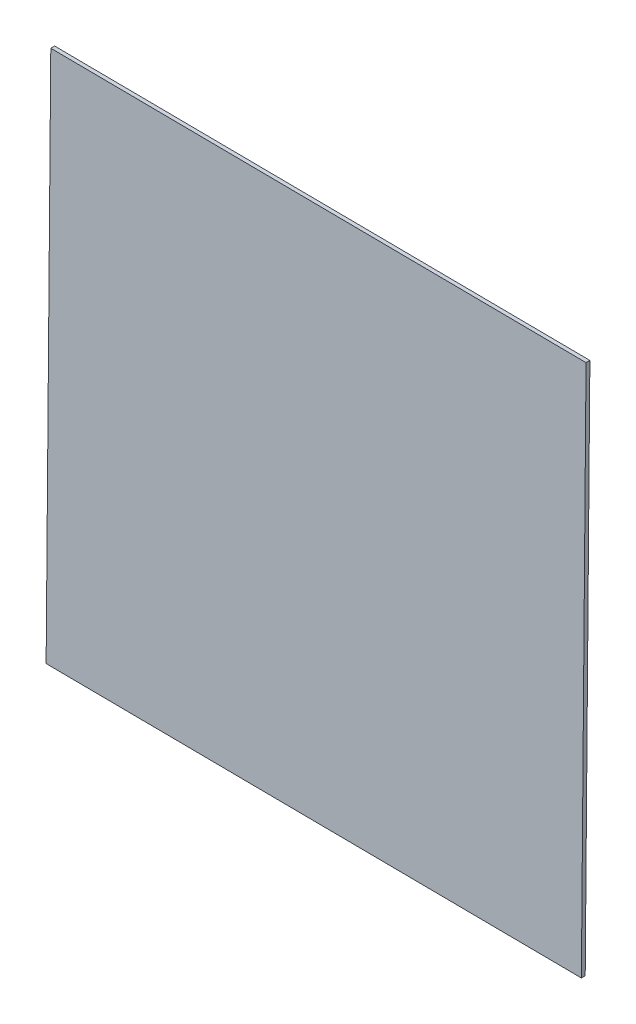
SolidWorks part; units mm, degrees
ref_plane "Front Plane" through (0, 0, 0) normal (0, 0, 1) x (1, 0, 0)
ref_plane "Top Plane" through (0, 0, 0) normal (0, 1, 0) x (1, 0, 0)
ref_plane "Right Plane" through (0, 0, 0) normal (1, 0, 0) x (0, 0, -1)
sketch "Sketch1" plane through (0, 0, 0) normal (0, 0, 1) x (1, 0, 0)
  line L4 (-97.7146, 56.2371) -> (-79.9861, 56.0824)
  line L5 (-79.9861, 56.0824) -> (-79.8314, 73.8109)
  line L6 (-79.8314, 73.8109) -> (-97.5599, 73.9656)
  line L7 (-97.5599, 73.9656) -> (-97.7146, 56.2371)
  line L8 (-97.7146, 56.2371) -> (-79.9861, 56.0824)
  line L9 (-79.9861, 56.0824) -> (-79.8314, 73.8109)
  line L10 (-79.8314, 73.8109) -> (-97.5599, 73.9656)
  line L11 (-97.5599, 73.9656) -> (-97.7146, 56.2371)
  dimension "D1" = 0
extrude "Boss-Extrude1" add sketch "Sketch1" along normal blind 0.127
sketch "Sketch2" plane through (0, 0, 0) normal (0, 0, -1) x (-1, 0, 0)
  line L0 (97.6376, 65.024) -> (79.9084, 65.024) construction
  line L1 (79.9861, 56.0824) -> (79.8314, 73.8109) construction
  line L2 (97.5599, 73.9656) -> (97.7146, 56.2371) construction
  line L3 (79.9084, 57.1754) -> (97.6376, 57.1754) construction
  line L4 (79.9328, 62.1919) -> (97.6627, 62.1919) construction
  line L7 (86.233, 57.1754) -> (89.1133, 57.1754)
  line L8 (89.1133, 57.1754) -> (91.313, 60.9854)
  line L9 (91.313, 60.9854) -> (88.4327, 60.9854)
  line L10 (88.4327, 60.9854) -> (86.233, 57.1754)
  line L11 (88.773, 73.8886) -> (88.773, 56.1594) construction
  line L14 (81.4477, 57.1754) -> (84.328, 57.1754)
  line L15 (84.328, 57.1754) -> (86.5277, 60.9854)
  line L16 (86.5277, 60.9854) -> (83.6474, 60.9854)
  line L17 (83.6474, 60.9854) -> (81.4477, 57.1754)
  line L18 (91.0183, 57.1754) -> (93.218, 60.9854)
  line L19 (93.218, 60.9854) -> (96.0983, 60.9854)
  line L20 (96.0983, 60.9854) -> (93.8986, 57.1754)
  line L21 (93.8986, 57.1754) -> (91.0183, 57.1754)
  line L22 (79.9084, 72.8726) -> (97.6376, 72.8726) construction
  line L23 (86.233, 69.0626) -> (89.1133, 69.0626)
  line L24 (89.1133, 69.0626) -> (91.313, 72.8726)
  line L25 (91.313, 72.8726) -> (88.4327, 72.8726)
  line L26 (88.4327, 72.8726) -> (86.233, 69.0626)
  line L27 (81.4477, 69.0626) -> (84.328, 69.0626)
  line L28 (84.328, 69.0626) -> (86.5277, 72.8726)
  line L29 (86.5277, 72.8726) -> (83.6474, 72.8726)
  line L30 (83.6474, 72.8726) -> (81.4477, 69.0626)
  line L31 (91.0183, 69.0626) -> (93.218, 72.8726)
  line L32 (93.218, 72.8726) -> (96.0983, 72.8726)
  line L33 (96.0983, 72.8726) -> (93.8986, 69.0626)
  line L34 (93.8986, 69.0626) -> (91.0183, 69.0626)
  line L35 (87.6731, 57.1754) -> (89.8729, 60.9854) construction
  text T0 "<b>FIRE</b>" font "GordonURWMed" height in points 24
  point P18 (87.6731, 57.1754)
  point P26 (89.8729, 60.9854)
  point P40 (87.6731, 69.0626)
  point P43 (89.8729, 72.8726)
  point P53 (88.773, 59.0804)
  dimension "D1" = 2.8321
wrap "FIRE" sketch "Sketch2" wrap type scribe source sketch "Sketch2" face at (-88.773, 65.024, 0)
sketch "Sketch3" [suppressed] plane through (0, 0, 0) normal (0, 0, -1) x (-1, 0, 0)
  line L0 (79.9084, 65.3056) -> (97.6376, 65.3056) construction
  line L3 (79.9084, 65.024) -> (97.6376, 65.024) construction
  line L4 (79.9084, 60.5059) -> (97.6376, 60.5059) construction
  line L5 (79.9084, 69.5421) -> (97.6376, 69.5421) construction
  line L6 (95.8049, 69.5421) -> (95.8049, 60.5059) construction
  text T0 "APU" font "GordonURWMed" height in points 18
  text T1 "FIRE" font "GordonURWMed" height in points 18
  point P15 (95.8049, 65.024)
wrap "APU FIRE" [suppressed] sketch "Sketch3" source sketch "Sketch3"
sketch "Sketch4" [suppressed] plane through (0, 0, 0) normal (0, 0, -1) x (-1, 0, 0)
  line L0 (79.9084, 65.4564) -> (97.6376, 65.4564) construction
  line L4 (79.9084, 65.024) -> (97.6376, 65.024) construction
  line L6 (79.9084, 61.4926) -> (97.6376, 61.4926) construction
  text T0 "MASTER" font "GordonURWMed" height in points 14
  text T1 "CAUTION" font "GordonURWMed" height in points 14
wrap "MC" [suppressed] sketch "Sketch4" source sketch "Sketch4"
